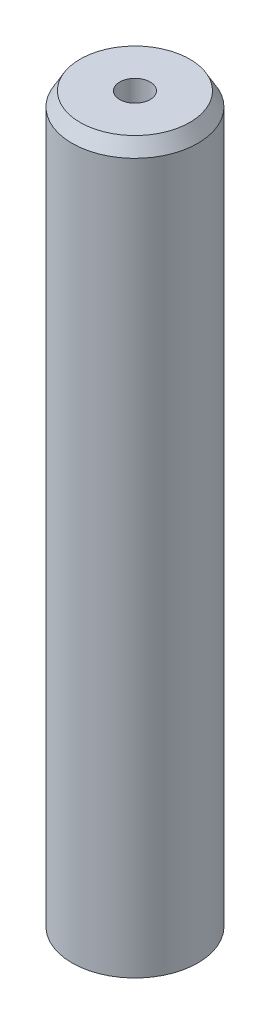
SolidWorks part; units mm, degrees
ref_plane "Front Plane" through (0, 0, 0) normal (0, 0, 1) x (1, 0, 0)
ref_plane "Top Plane" through (0, 0, 0) normal (0, 1, 0) x (1, 0, 0)
ref_plane "Right Plane" through (0, 0, 0) normal (1, 0, 0) x (0, 0, -1)
sketch "Sketch1" plane through (0, 0, 0) normal (0, 1, 0) x (1, 0, 0)
  circle A0 centre (0, 0) radius 7.5
  dimension "SHAFT_OD" = 15
extrude "Boss-Extrude1" add sketch "Sketch1" along normal blind 87.2146
sketch "Sketch2" plane through (0, 0, 0) normal (0, 1, 0) x (1, 0, 0)
  circle A0 centre (0, 0) radius 1.8155
  dimension "BORE_D" = 3.6309
extrude "Cut-Extrude1" cut sketch "Sketch2" along normal through all
chamfer "Chamfer1" distance 1.671 angle 30 2 edges at (0, 87.2146, 7.5) (0, 0, 7.5) first distance on face at (0, 87.2146, 7.5) first distance on face at (0, 0, 1.8155)
